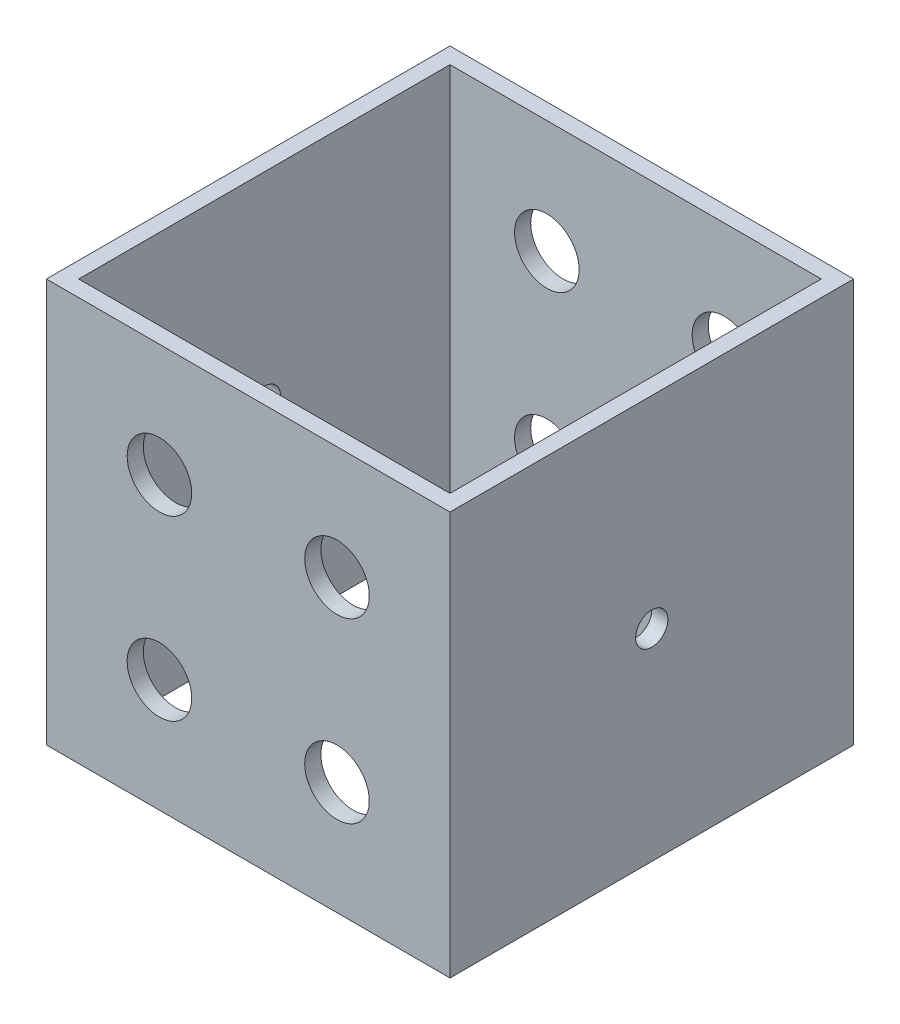
SolidWorks part; units mm, degrees
ref_plane "Front Plane" through (0, 0, 0) normal (0, 0, 1) x (1, 0, 0)
ref_plane "Top Plane" through (0, 0, 0) normal (0, 1, 0) x (1, 0, 0)
ref_plane "Right Plane" through (0, 0, 0) normal (1, 0, 0) x (0, 0, -1)
sketch "Sketch1" plane through (0, 0, 0) normal (0, 1, 0) x (1, 0, 0)
  line L0 (0, 43.992) -> (0, -43.1735) construction
  line L1 (-56.8827, 0) -> (56.8827, 0) construction
  line L3 (-11.5, 11.5) -> (11.5, 11.5)
  line L4 (-11.5, 11.5) -> (-11.5, -11.5)
  line L5 (-11.5, -11.5) -> (11.5, -11.5)
  line L6 (11.5, 11.5) -> (11.5, -11.5)
  line L7 (-11.5, 11.5) -> (11.5, -11.5) construction
  line L8 (-11.5, -11.5) -> (11.5, 11.5) construction
  line L9 (-12.5, 12.5) -> (12.5, 12.5)
  line L10 (-12.5, 12.5) -> (-12.5, -12.5)
  line L11 (-12.5, -12.5) -> (12.5, -12.5)
  line L12 (12.5, 12.5) -> (12.5, -12.5)
  line L13 (-12.5, 12.5) -> (12.5, -12.5) construction
  line L14 (-12.5, -12.5) -> (12.5, 12.5) construction
  point P5 (0, 0)
  point P10 (0, 0)
extrude "Boss-Extrude1" add sketch "Sketch1" along normal blind 12.5 and the other way blind 12.5
sketch "Sketch2" plane through (0, 0, -12.5) normal (0, 0, -1) x (-1, 0, 0)
  line L0 (12.5, -12.5) -> (12.5, 12.5) construction
  line L2 (-12.5, 12.5) -> (12.5, 12.5) construction
  line L6 (-12.5, -12.5) -> (-12.5, 12.5) construction
  circle A0 centre (5.5, 5.5) radius 2
  circle A1 centre (5.5, -5.5) radius 2
  circle A2 centre (-5.5, -5.5) radius 2
  circle A3 centre (-5.5, 5.5) radius 2
  point P10 (0, 0)
  dimension "D1" = 7
  dimension "D2" = 11
  dimension "D3" = 7
  dimension "D4" = 7
  dimension "D5" = 11
  dimension "D6" = 11
  dimension "D7" = 7
  dimension "D8" = 11
extrude "Cut-Extrude1" cut sketch "Sketch2" against normal blind 25
sketch "Sketch3" plane through (12.5, 0, 0) normal (1, 0, 0) x (0, 0, -1)
  circle A0 centre (0, 0) radius 1
extrude "Cut-Extrude2" cut sketch "Sketch3" against normal blind 25 contours A0
